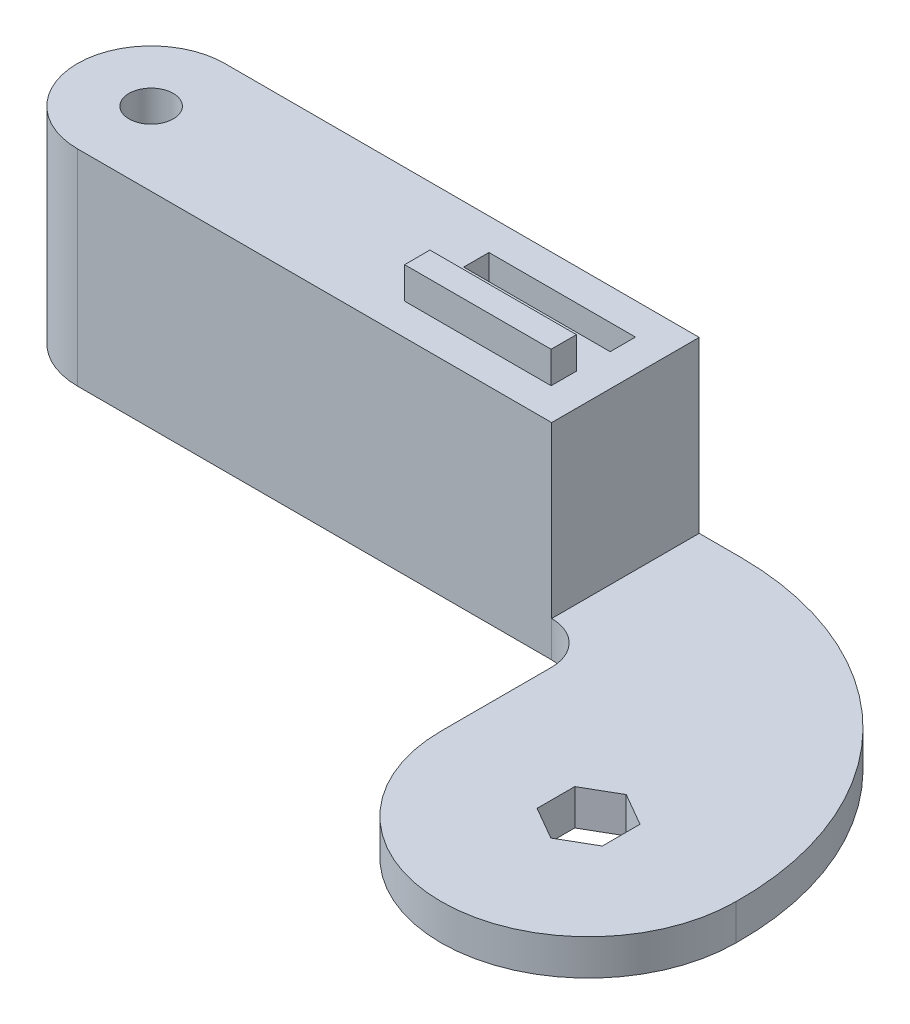
SolidWorks part; units mm, degrees
ref_plane "Front Plane" through (0, 0, 0) normal (0, 0, 1) x (1, 0, 0)
ref_plane "Top Plane" through (0, 0, 0) normal (0, 1, 0) x (1, 0, 0)
ref_plane "Right Plane" through (0, 0, 0) normal (1, 0, 0) x (0, 0, -1)
sketch "Эскиз1" plane through (0, 0, 0) normal (0, 1, 0) x (1, 0, 0)
  line L11 (-28, 0) -> (-28, 21)
  line L12 (-36, 29) -> (-140, 29)
  line L13 (-140, 29) -> (-140, 57)
  line L14 (-28, 0) -> (-28, 57)
  line L15 (-28, 57) -> (-140, 57)
  circle A1 centre (0, 0) radius 28
  arc A6 (28, 0) -> (-28, 57) centre (-28.1947, 0.8) ccw
  arc A7 (-36, 29) -> (-28, 21) centre (-36, 21) cw
  dimension "D1" = 56
  dimension "D4" = 8
  dimension "D6" = 56.2004
  dimension "D2" = 29
  dimension "D5" = 140
  dimension "D3" = 28
extrude "Бобышка-Вытянуть1" add sketch "Эскиз1" along normal blind 6.8 contours L12 A7 L14 L15 L13 | A1 A6 L14 L11 | A1 region at (-8.1564, 0, -36.025) region at (0, 0, 0) region at (-83.7636, 0, -42.9312)
sketch "Эскиз2" plane through (0, 6.8, 0) normal (0, 1, 0) x (1, 0, 0)
  line L1 (0, 7.15) -> (-6.1921, 3.575)
  line L2 (-6.1921, 3.575) -> (-6.1921, -3.575)
  line L3 (-6.1921, -3.575) -> (0, -7.15)
  line L4 (0, -7.15) -> (6.1921, -3.575)
  line L5 (6.1921, -3.575) -> (6.1921, 3.575)
  line L6 (6.1921, 3.575) -> (0, 7.15)
  circle A0 centre (0, 0) radius 6.1921 construction
  dimension "D1" = 14.3
extrude "Вырез-Вытянуть1" cut sketch "Эскиз2" against normal blind 6.9
sketch "Эскиз3" plane through (0, 6.8, 0) normal (0, 1, 0) x (1, 0, 0)
  line L1 (-140, 29) -> (-36, 29)
  line L2 (-140, 29) -> (-140, 57)
  line L3 (-140, 57) -> (-36, 57)
  line L4 (-36, 29) -> (-36, 57)
  dimension "D1" = 104
extrude "Бобышка-Вытянуть2" add sketch "Эскиз3" along normal blind 32.2
sketch "Эскиз4" plane through (0, 39, 0) normal (0, 1, 0) x (1, 0, 0)
  line L5 (-42.1, 51) -> (-69.9, 51)
  line L6 (-42.1, 51) -> (-42.1, 46.2)
  line L7 (-42.1, 46.2) -> (-69.9, 46.2)
  line L8 (-69.9, 51) -> (-69.9, 46.2)
  line L9 (-42.1, 35) -> (-69.9, 35)
  line L10 (-42.1, 35) -> (-42.1, 39.8)
  line L11 (-42.1, 39.8) -> (-69.9, 39.8)
  line L12 (-69.9, 35) -> (-69.9, 39.8)
  line L17 (-36, 57) -> (-140, 57) construction
  line L19 (-140, 29) -> (-36, 29) construction
  line L20 (-36, 29) -> (-36, 57) construction
  dimension "D9" = 6.1
  dimension "D10" = 6.1
  dimension "D11" = 6
  dimension "D12" = 6
  dimension "D13" = 4.8
  dimension "D14" = 4.8
  dimension "D15" = 27.8
  dimension "D16" = 27.8
extrude "Вырез-Вытянуть2" cut sketch "Эскиз4" against normal blind 6 contours L5 L8 L7 L6 region at (-56, 39, -48.6)
extrude "Бобышка-Вытянуть3" add sketch "Эскиз4<3>" along normal blind 6 contours L12 L9 L10 L11 region at (-56, 39, -37.4)
sketch "Эскиз4<3>" plane through (0, 39, 0) normal (0, 1, 0) x (1, 0, 0) same geometry as "Эскиз4"
sketch "Эскиз5" plane through (0, 0, 0) normal (0, -1, 0) x (1, 0, 0)
  line L0 (-36, -29) -> (-140, -29) construction
  line L1 (-133, -36) -> (-119, -36)
  line L2 (-133, -36) -> (-133, -50)
  line L3 (-133, -50) -> (-119, -50)
  line L4 (-119, -36) -> (-119, -50)
  line L5 (-140, -29) -> (-140, -57) construction
  dimension "D1" = 7
  dimension "D2" = 7
  dimension "D3" = 14
  dimension "D4" = 14
extrude "Вырез-Вытянуть3" cut sketch "Эскиз5" against normal blind 14
sketch "Эскиз6" plane through (0, 14, 0) normal (0, -1, 0) x (1, 0, 0)
  circle A0 centre (-126, -43) radius 4.2
  dimension "D1" = 8.4
extrude "Вырез-Вытянуть4" cut sketch "Эскиз6" against normal through all
fillet "Скругление1" radius 14 2 edges at (-140, 19.5, -29) (-140, 19.5, -57)
